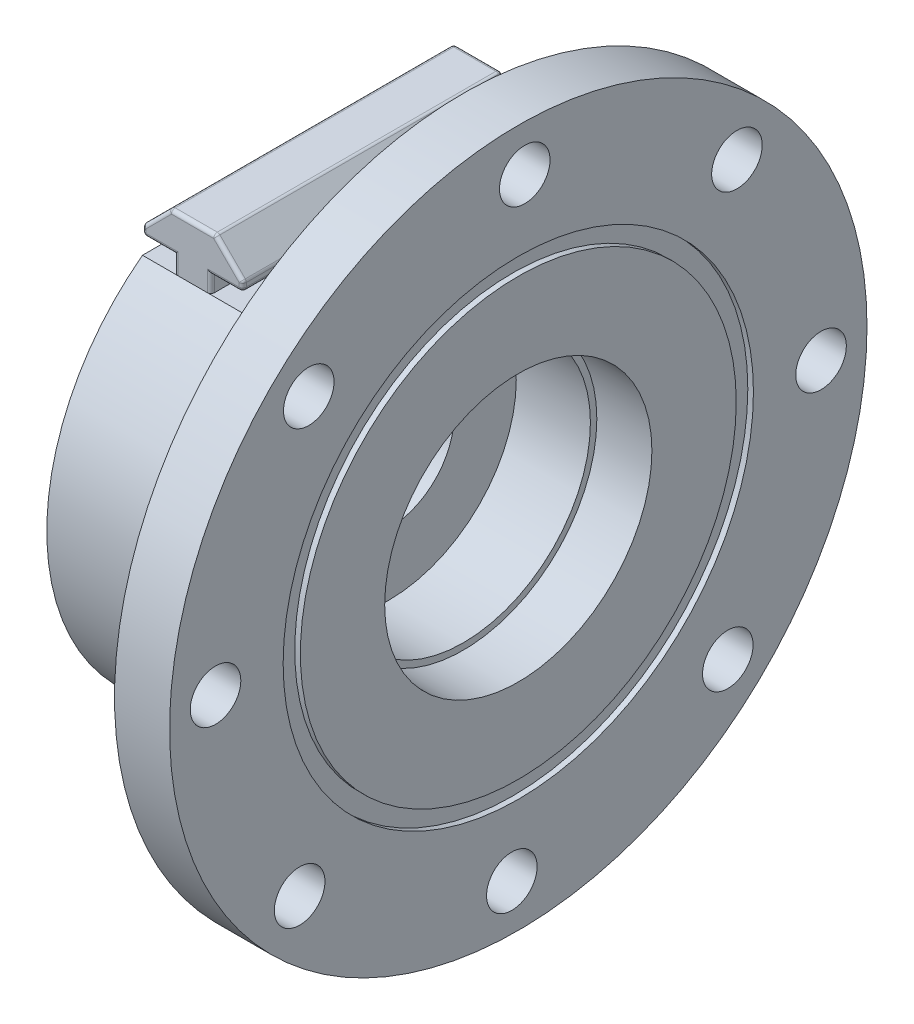
SolidWorks part; units mm, degrees
ref_plane "Front Plane" through (0, 0, 0) normal (0, 0, 1) x (1, 0, 0)
ref_plane "Top Plane" through (0, 0, 0) normal (0, 1, 0) x (1, 0, 0)
ref_plane "Right Plane" through (0, 0, 0) normal (1, 0, 0) x (0, 0, -1)
sketch "Main sketch" plane through (0, 0, 0) normal (0, 0, 1) x (1, 0, 0)
  line L0 (0, 9) -> (0, 19.995)
  line L1 (0, 19.995) -> (-8, 19.995)
  line L2 (-8, 19.995) -> (-8, 33.02)
  line L3 (-8, 33.02) -> (16.6116, 33.02)
  line L4 (16.6116, 33.02) -> (16.6116, 48.26)
  line L5 (16.6116, 48.26) -> (24.2316, 48.26)
  line L6 (24.2316, 48.26) -> (24.2316, 32.5438)
  line L7 (24.2316, 32.5438) -> (23.4537, 32.5438)
  line L8 (23.4537, 32.5438) -> (23.4537, 30.1625)
  line L9 (23.4537, 30.1625) -> (24.2316, 30.1625)
  line L10 (24.2316, 30.1625) -> (24.2316, 18.4912)
  line L11 (24.2316, 18.4912) -> (16.6116, 18.4912)
  line L12 (16.6116, 18.4912) -> (16.6116, 17.6022)
  line L13 (16.6116, 17.6022) -> (6.35, 17.6022)
  line L14 (6.35, 17.6022) -> (6.35, 9)
  line L15 (6.35, 9) -> (0, 9)
  line L16 (0, 0) -> (0, 9) construction
  dimension "D1" = 9
  dimension "D2" = 19.995
  dimension "D4" = 17.6022
  dimension "D5" = 8
  dimension "D6" = 48.26
  dimension "D7" = 18.4912
  dimension "D8" = 32.5437
  dimension "D11" = 6.35
  dimension "D12" = 10.2616
  dimension "D13" = 33.02
  dimension "D14" = 7.62
  dimension "D9" = 30.1625
  dimension "D10" = 0.7779
  dimension "D3" = 7.62
ref_axis "Axis1" through (71.9501, 0, 0) along (-1, 0, 0)
revolve "Revolve1" add sketch "Main sketch" angle 360 about axis through (71.9501, 0, 0) along (-1, 0, 0)
sketch "Sketch2" plane through (24.2316, 0, 0) normal (1, 0, 0) x (0, 0, -1)
  circle A0 centre (0, 0) radius 41.91 construction
  point P0 (0, 0)
  point P3 (-41.9005, 0.8944)
  point P4 (-30.2606, -28.9956)
  point P7 (-0.8944, -41.9005)
  point P8 (28.9956, -30.2606)
  point P9 (41.9005, -0.8944)
  point P10 (30.2606, 28.9956)
  point P11 (0.8944, 41.9005)
  point P12 (-28.9956, 30.2606)
  point P13 (0, 0)
  point P16 (0, 0)
  dimension "D2" = 83.82
  dimension "D1" = 8
hole_wizard "M6 Clearance Hole1" positions "Sketch2" profile "Sketch3" hole size "M6" standard "ISO" end condition through all
sketch "Sketch3" plane through (24.2316, 0, 0) normal (0, 1, 0) x (0, 0, -1)
  line L0 (0, 0) -> (0, 32.2316)
  line L1 (0, 32.2316) -> (3.5, 32.2316)
  line L2 (3.5, 32.2316) -> (3.5, 0)
  line L5 (3.5, 0) -> (0, 0)
  line L11 (0, -6.35) -> (0, 107.95) construction
  dimension "Thru Hole Dia." = 7
  dimension "Thru Hole Depth" = 32.2316
ref_plane "Plane1" through (0, 0, 33.02) normal (0, 0, 1) x (1, 0, 0)
ref_plane "Plane2" through (0, 33.02, 0) normal (0, 1, 0) x (1, 0, 0)
ref_plane "Plane3" through (0, 0, -33.02) normal (0, 0, -1) x (-1, 0, 0)
sketch "Sketch4" plane through (0, 33.02, 0) normal (0, 1, 0) x (1, 0, 0)
  line L0 (-8, -33.02) -> (16.6116, -33.02) construction
  line L1 (16.6116, 33.02) -> (16.6116, -33.02) construction
  line L2 (16.6116, 33.02) -> (-8, 33.02) construction
  line L3 (-8, 33.02) -> (-8, -33.02) construction
  line L4 (-8, -33.02) -> (16.6116, -33.02)
  line L5 (16.6116, 33.02) -> (16.6116, -33.02)
  line L6 (16.6116, 33.02) -> (-8, 33.02)
  line L7 (-8, 33.02) -> (-8, -33.02)
extrude "Cut-Extrude1" cut sketch "Sketch4" against normal blind 6.5786
ref_plane "Plane4" through (0, 0, -19.7781) normal (0, 0, 1) x (1, 0, 0)
ref_plane "Plane5" through (0, 0, 19.7781) normal (0, 0, -1) x (-1, 0, 0)
sketch "Sketch5" plane through (0, 0, 19.7781) normal (0, 0, -1) x (-1, 0, 0)
  line L0 (8, 26.4414) -> (-16.6116, 26.4414) construction
  line L1 (8, 26.4414) -> (-16.6116, 26.4414)
  line L2 (-1.4742, 26.4414) -> (-1.4742, 28.8036)
  line L3 (-1.4742, 28.8036) -> (-5.8684, 28.8036)
  line L4 (-5.8684, 28.8036) -> (-5.8684, 30.0736)
  line L5 (-5.8684, 30.0736) -> (-2.0584, 33.8836)
  line L6 (-2.0584, 33.8836) -> (4.19, 33.8836)
  line L7 (1.0658, 33.8836) -> (1.0658, 26.4414) construction
  line L8 (3.6058, 26.4414) -> (-1.4742, 26.4414)
  line L9 (3.6058, 26.4414) -> (3.6058, 28.8036)
  line L10 (3.6058, 28.8036) -> (8, 28.8036)
  line L11 (8, 28.8036) -> (8, 30.0736)
  line L12 (8, 30.0736) -> (4.19, 33.8836)
  line L13 (8, -33.02) -> (8, 26.4414) construction
  dimension "D1" = 2.54
  dimension "D2" = 2.3622
  dimension "D3" = 135
  dimension "D4" = 5.08
  dimension "D5" = 6.9342
  dimension "D6" = 1.27
extrude "Boss-Extrude1" add sketch "Sketch5" along normal up to surface (39.5562 mm away) contours L7 L6 L5 L4 L3 L2 L8 | L6 L7 L1 L9 L10 L11 L12 region at (-3.6753, 30.4149, 19.7781) region at (1.5437, 30.4149, 19.7781) up to plane "Plane4"
fillet "Fillet1" radius 0.508 24 edges at (-1.0658, 33.8836, -19.7781) (1.4742, 27.6225, 19.7781) (5.8684, 29.4386, 19.7781) (3.6713, 28.8036, 19.7781) (3.9634, 31.9786, 19.7781) (-1.0658, 33.8836, 19.7781) (-5.8029, 28.8036, 19.7781) (-3.6058, 27.6225, 19.7781) (1.4742, 27.6225, -19.7781) (-3.6058, 27.6225, -19.7781) (-5.8029, 28.8036, -19.7781) (-6.095, 31.9786, -19.7781) (-4.19, 33.8836, 0) (-6.095, 31.9786, 19.7781) (-8, 29.4386, 19.7781) (-8, 30.0736, 0) (-8, 28.8036, 0) (-8, 29.4386, -19.7781) (3.9634, 31.9786, -19.7781) (5.8684, 29.4386, -19.7781) (3.6713, 28.8036, -19.7781) (2.0584, 33.8836, 0) (5.8684, 30.0736, 0) (5.8684, 28.8036, 0)
mirror "Mirror1" about plane through (0, 0, 0) normal (0, 1, 0) of "Fillet1", "Boss-Extrude1", "Cut-Extrude1"
equation "\"Shaft_OD\"= 17mm'outer diameter of shaft"
equation "\"O_Ring_ID\"= 2.375in"
equation "\"O_Ring_CS\"= 1 / 16in'cross section"
equation "\"Bearing_OD\"= 39.99mm"
equation "\"Bearing_Depth\"= 8mm'depth bearing goes into the casing"
equation "\"Stationary_Face_Seal_OD\"= 1.386in"
equation "\"Flange_Dia\"= 3.8in"
equation "\"Screw_Dia\"= 6mm"
equation "\"Seal_Space\"= .3in"
equation "\"D1@Main sketch\"=\"Shaft_OD\" / 2 + .5mm"
equation "\"D2@Main sketch\" = \"Bearing_OD\" / 2"
equation "\"D4@Main sketch\" = \"Stationary_Face_Seal_OD\" / 2"
equation "\"D5@Main sketch\" = \"Bearing_Depth\""
equation "\"D6@Main sketch\" = \"Flange_Dia\" / 2"
equation "\"Seal_Area_Dia\"= 37mm"
equation "\"D7@Main sketch\"=\"Seal_space_Dia\"/2"
equation "\"D8@Main sketch\"=\"O_Ring_ID\" / 2 + \"O_Ring_CS\" * 1.5"
equation "\"Face_Seal_Height\"= 0.404in"
equation "\"D12@Main sketch\" = \"Face_Seal_Height\""
equation "\"Housing_OR\"= 1.3in'Outer radius of housing"
equation "\"D13@Main sketch\"=\"Housing_OR\""
equation "\"D10@Main sketch\"=\"O_Ring_CS\"*.49"
equation "\"D9@Main sketch\"=\"O_Ring_ID\"/2"
equation "\"D2@Sketch2\"=\"Flange_Dia\"-\"Screw_offset\""
equation "\"Screw_offset\"= .5in'offset of screws from flange OD."
equation "\"Seal_space_Dia\"= \"Stationary_Face_Seal_OD\" + .07'diameter of the space for the face seal"
